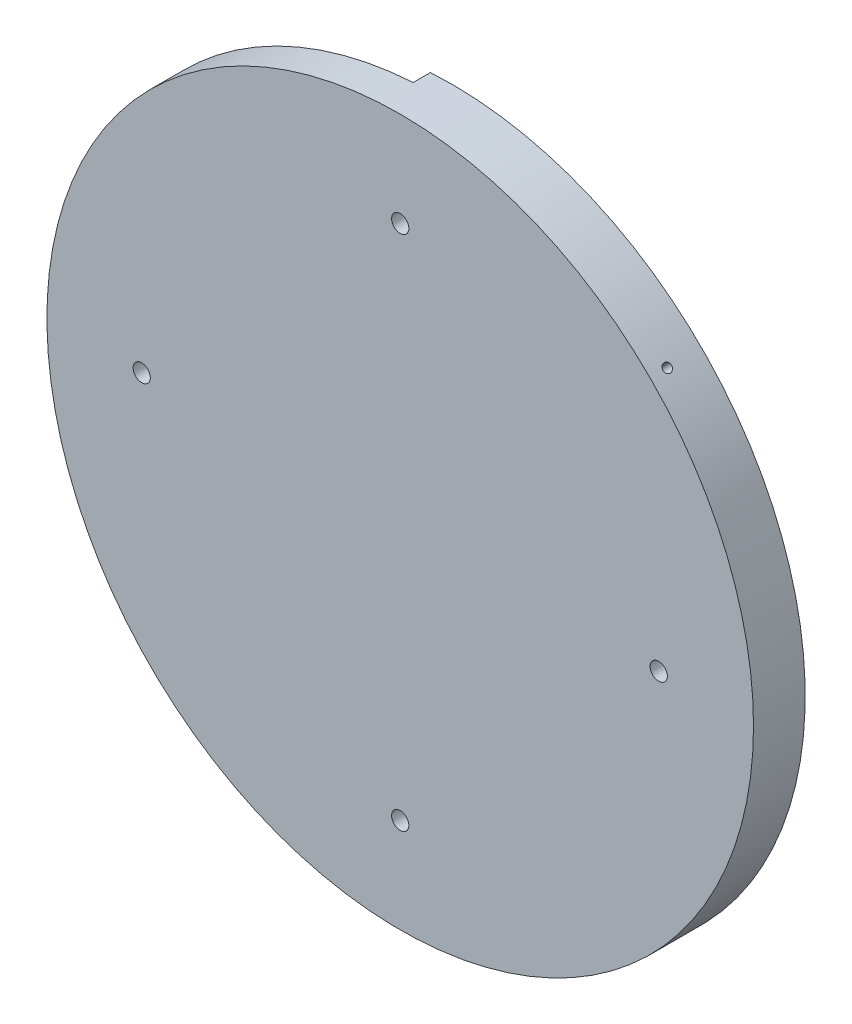
SolidWorks part; units mm, degrees
ref_plane "Front Plane" through (0, 0, 0) normal (0, 0, 1) x (1, 0, 0)
ref_plane "Top Plane" through (0, 0, 0) normal (0, 1, 0) x (1, 0, 0)
ref_plane "Right Plane" through (0, 0, 0) normal (1, 0, 0) x (0, 0, -1)
sketch "Sketch1" plane through (0, 0, 0) normal (0, 0, 1) x (1, 0, 0)
  circle A0 centre (0, 0) radius 82
  dimension "D1" = 164
extrude "Boss-Extrude1" add sketch "Sketch1" along normal blind 8
sketch "Sketch3" plane through (0, 0, 0) normal (0, 0, -1) x (-1, 0, 0)
  line L0 (5, 81.8474) -> (5, 75.3343)
  line L1 (5, -75.3343) -> (5, -81.8474)
  arc A0 (5, 75.3343) -> (5, -75.3343) centre (0, 0) ccw
  circle A1 centre (0, 0) radius 82 construction
  arc A2 (5, 81.8474) -> (5, -81.8474) centre (0, 0) ccw
  dimension "D1" = 151
  dimension "D2" = 5
extrude "Boss-Extrude3" add sketch "Sketch3" along normal blind 4
fillet "Fillet1" radius 10 2 edges at (-5, 75.3343, -2) (-5, -75.3343, -2)
sketch "Sketch2" plane through (0, 0, 8) normal (0, 0, 1) x (1, 0, 0)
  circle A0 centre (0, 60) radius 2
  dimension "D1" = 4
  dimension "D2" = 60
extrude "Cut-Extrude1" cut sketch "Sketch2" against normal blind 15
pattern_circular "CirPattern2" count 4 every 90 about axis through (0, 0, 0) along (0, 0, 1) of "Cut-Extrude1"
sketch "Sketch7" plane through (0, 0, 0) normal (0, 0, -1) x (-1, 0, 0)
  line L7 (1.7885, 63.6242) -> (-2.2444, 63.3609)
  line L8 (-2.2444, 63.3609) -> (-4.0329, 59.7368)
  line L9 (-4.0329, 59.7368) -> (-1.7885, 56.3758)
  line L10 (-1.7885, 56.3758) -> (2.2444, 56.6391)
  line L11 (2.2444, 56.6391) -> (4.0329, 60.2632)
  line L12 (4.0329, 60.2632) -> (1.7885, 63.6242)
  circle A0 centre (0, 60) radius 3.5 construction
  point P30 (36.3101, 9.0679)
  dimension "D1" = 7
extrude "Cut-Extrude3" cut sketch "Sketch7" against normal blind 3.2
pattern_circular "CirPattern3" count 4 every 90 about axis through (0, 0, 0) along (0, 0, 1) of "Cut-Extrude3"
ref_plane "Plane1" through (0, 0, 0) normal (-0.7071, 0.7071, 0) x (0.7071, 0.7071, 0)
ref_plane "Plane2" through (-57.9828, 57.9828, 0) normal (-0.7071, 0.7071, 0) x (0.7071, 0.7071, 0)
sketch "Sketch8" plane through (-57.9828, 57.9828, 0) normal (-0.7071, 0.7071, 0) x (0.7071, 0.7071, 0)
  line L0 (75.5, 0) -> (-50.6001, 0) construction
  circle A0 centre (0, -4) radius 1
  dimension "D1" = 2
  dimension "D2" = 4
extrude "Cut-Extrude4" cut sketch "Sketch8" against normal blind 12
pattern_circular "CirPattern4" count 4 every 90 about axis through (0, 0, 0) along (0, 0, 1) of "Cut-Extrude4"
